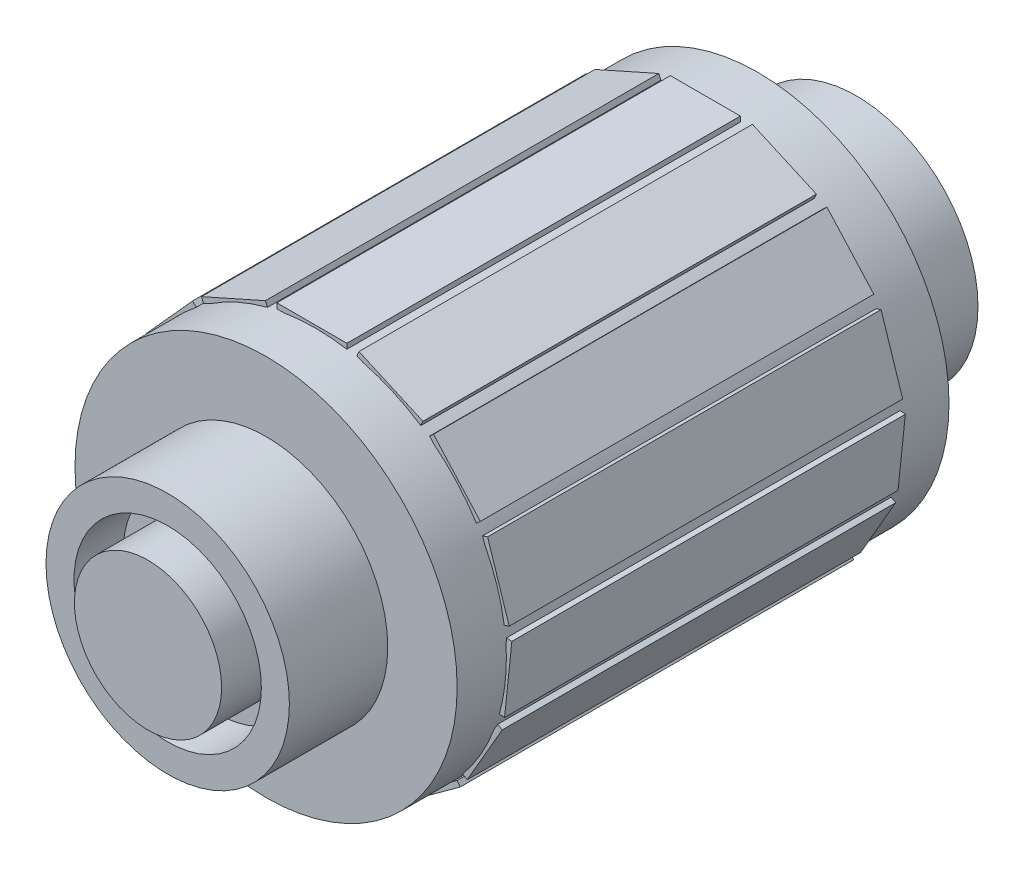
SolidWorks part; units mm, degrees
ref_plane "Front Plane" through (0, 0, 0) normal (0, 0, 1) x (1, 0, 0)
ref_plane "Top Plane" through (0, 0, 0) normal (0, 1, 0) x (1, 0, 0)
ref_plane "Right Plane" through (0, 0, 0) normal (1, 0, 0) x (0, 0, -1)
sketch "Sketch1" plane through (0, 0, 0) normal (0, 0, 1) x (1, 0, 0)
  circle A0 centre (0, 0) radius 12.37
extrude "Boss-Extrude1" add sketch "Sketch1" along normal blind 10
sketch "Sketch2" plane through (0, 0, 10) normal (0, 0, 1) x (1, 0, 0)
  circle A0 centre (0, 0) radius 19.4232
extrude "Boss-Extrude2" add sketch "Sketch2" along normal blind 50
sketch "Sketch4" plane through (0, 0, 60) normal (0, 0, 1) x (1, 0, 0)
  circle A0 centre (0, 0) radius 12.37 construction
  circle A1 centre (0, 0) radius 12.37
extrude "Boss-Extrude3" add sketch "Sketch4" along normal blind 10
sketch "Sketch5" plane through (0, 0, 60) normal (0, 0, 1) x (1, 0, 0)
  line L1 (-3.9013, 19.685) -> (3.2145, 19.685)
  line L2 (-3.9013, 19.685) -> (-3.9013, 19.1553)
  line L3 (-3.9013, 19.1553) -> (3.2145, 19.1553)
  line L4 (3.2145, 19.685) -> (3.2145, 19.1553)
  line L5 (-3.9013, 19.685) -> (3.2145, 19.1553) construction
  line L6 (-3.9013, 19.1553) -> (3.2145, 19.685) construction
  circle A0 centre (0, 0) radius 19.4232 construction
  point P0 (-0.3434, 19.4202)
extrude "Boss-Extrude4" add sketch "Sketch5" against normal blind 40 from offset 5 offset against normal yes
pattern_circular "CirPattern1" count 15 over 360 of "Boss-Extrude4"
sketch "Sketch6" plane through (0, 0, 70) normal (0, 0, 1) x (1, 0, 0)
  circle A0 centre (0, 0) radius 9.5213
extrude "Cut-Extrude1" cut sketch "Sketch6" against normal blind 5
sketch "Sketch7" plane through (0, 0, 0) normal (0, 0, -1) x (-1, 0, 0)
  circle A1 centre (0, 0) radius 9.5213
  circle A2 centre (0, 0) radius 9.5213
  dimension "D1" = 0
extrude "Cut-Extrude2" cut sketch "Sketch7" against normal blind 5
sketch "Sketch8" plane through (0, 0, 5) normal (0, 0, -1) x (-1, 0, 0)
  circle A0 centre (0, 0) radius 7.4816
extrude "Boss-Extrude5" add sketch "Sketch8" along normal blind 7
sketch "Sketch9" plane through (0, 0, 65) normal (0, 0, 1) x (1, 0, 0)
  circle A1 centre (0, 0) radius 7.4816
  circle A2 centre (0, 0) radius 7.4816
  dimension "D1" = 0
extrude "Boss-Extrude6" add sketch "Sketch9" along normal blind 7
